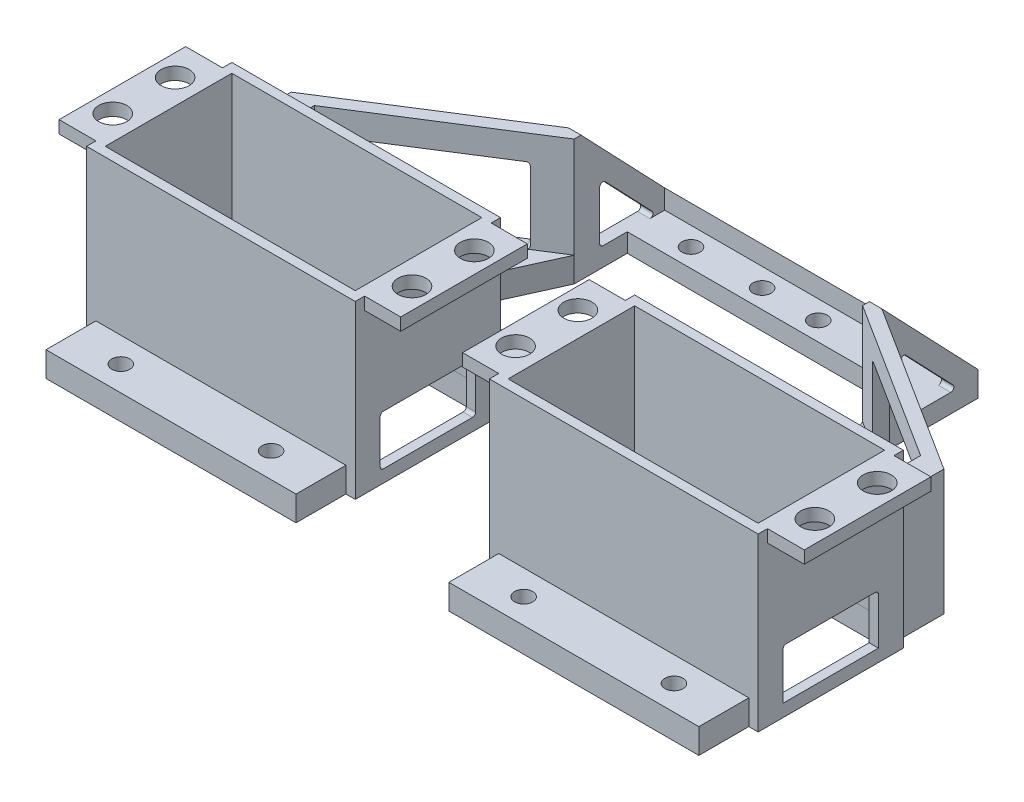
SolidWorks part; units mm, degrees
material "PLA"
ref_plane "Front Plane" through (0, 0, 0) normal (0, 0, 1) x (1, 0, 0)
ref_plane "Top Plane" through (0, 0, 0) normal (0, 1, 0) x (1, 0, 0)
ref_plane "Right Plane" through (0, 0, 0) normal (1, 0, 0) x (0, 0, -1)
sketch "Sketch1" plane through (0, 0, 0) normal (0, 1, 0) x (1, 0, 0)
  line L0 (-59.76, 0) -> (59.76, 0) construction
  line L1 (0, -37.87) -> (0, 37.87) construction
  line L2 (-52.3548, -24.6209) -> (-52.3524, -4.3209)
  line L5 (-52.3524, -4.3209) -> (-12.2524, -4.3257)
  line L8 (-59.76, -37.87) -> (-59.76, -14.47) construction
  line L9 (-59.76, -37.87) -> (59.76, -37.87) construction
  line L10 (-59.76, -37.87) -> (-59.76, 37.87) construction
  line L11 (-59.76, 37.87) -> (59.76, 37.87) construction
  line L12 (59.76, -37.87) -> (59.76, 37.87) construction
  line L13 (-12.2524, -4.3257) -> (-12.2548, -24.6257)
  line L14 (-12.2548, -24.6257) -> (-52.3548, -24.6209)
  line L15 (-53.8522, -2.8207) -> (-10.7522, -2.8259)
  line L16 (-10.7522, -2.8259) -> (-10.755, -26.1259)
  line L17 (-10.755, -26.1259) -> (-53.855, -26.1207)
  line L18 (-53.855, -26.1207) -> (-53.8522, -2.8207)
  line L19 (-52.3524, -2.8209) -> (-52.3524, 5.1743)
  line L20 (-52.3524, 5.1743) -> (-12.2524, 5.1743)
  line L21 (-12.2524, 5.1743) -> (-12.2524, -2.8257)
  line L22 (-52.3548, -26.1209) -> (-52.3548, -34.1257)
  line L23 (-52.3548, -34.1257) -> (-12.2548, -34.1257)
  line L24 (-12.2548, -34.1257) -> (-12.2548, -26.1257)
  line L25 (-25.1261, 37.87) -> (0, 37.87)
  line L26 (-25.1261, 37.87) -> (-25.1261, 22.4543)
  line L27 (-25.1261, 22.4543) -> (-52.3524, 5.1743)
  line L28 (0, 37.87) -> (0, 35.87)
  line L29 (0, 35.87) -> (-23.1261, 35.87)
  line L30 (-23.1261, 35.87) -> (-23.1261, 21.3549)
  line L31 (-23.1261, 21.3549) -> (-48.6201, 5.1743)
  point P5 (0, 0)
  point P6 (0, 0)
  point P7 (-59.76, -14.47)
  point P32 (0, 37.87)
  line B0 (-52.3548, -24.6209) -> (-52.3524, -4.3209) construction
  line B1 (-4.9588, -4.3265) -> (-59.7588, -4.32) construction
  line B2 (-4.9612, -24.6265) -> (-4.9588, -4.3265) construction
  line B3 (-12.2548, -24.6257) -> (-12.2524, -4.3257) construction
  line B4 (-4.9612, -24.6265) -> (-59.7612, -24.62) construction
  line B5 (-59.7588, -4.32) -> (-59.7612, -24.62) construction
  circle B6 centre (-8.3042, -19.4761) radius 2.25 construction
  circle B7 centre (-8.303, -9.4761) radius 2.25 construction
  circle B8 centre (-56.303, -9.4704) radius 2.25 construction
  circle B9 centre (-56.3042, -19.4704) radius 2.25 construction
  dimension "D1" = 119.52
  dimension "D2" = 75.74
  dimension "D3" = 1.5
  dimension "D4" = 23.4
  dimension "D5" = 8
  dimension "D6" = 8
  dimension "D7" = 2
  dimension "D8" = 2
  dimension "D9" = 2
  dimension "D10" = 17.28
sketch_block_instance "Block2-1"
sketch_block "Block2"
extrude "Boss-Extrude1" add sketch "Sketch1" along normal blind 4 contours L31 L30 L29 L28 L25 L26 L27 L20 | L21 L20 L19 L15 | L18 L17 L16 L15 L13 L14 L2 L5 | L23 L24 L17 L22 region at (-53.1023, 0, 3.3108) region at (-32.3004, 0, -1.1755) region at (-38.4085, 0, -13.2932) region at (-32.3068, 0, 30.1245)
sketch "Sketch2" plane through (0, 4, 0) normal (0, 1, 0) x (1, 0, 0)
  line L1 (-48.6201, 5.1743) -> (-23.1261, 21.3549)
  line L2 (-23.1261, 21.3549) -> (-23.1261, 35.87)
  line L3 (-23.1261, 35.87) -> (0, 35.87)
  line L4 (0, 35.87) -> (0, 37.87)
  line L5 (0, 37.87) -> (-25.1261, 37.87)
  line L6 (-25.1261, 37.87) -> (-25.1261, 22.4543)
  line L7 (-25.1261, 22.4543) -> (-52.3524, 5.1743)
  line L8 (-53.8522, -2.8207) -> (-10.7522, -2.8259)
  line L9 (-10.7522, -2.8259) -> (-10.755, -26.1259)
  line L10 (-10.755, -26.1259) -> (-53.855, -26.1207)
  line L11 (-53.855, -26.1207) -> (-53.8522, -2.8207)
  line L12 (-48.6201, 5.1743) -> (-48.6201, -2.8213)
  line L13 (-52.3548, -24.6209) -> (-12.2524, -24.6209)
  line L14 (-52.3548, -24.6209) -> (-52.3548, -4.3257)
  line L15 (-52.3548, -4.3257) -> (-12.2524, -4.3257)
  line L16 (-12.2524, -24.6209) -> (-12.2524, -4.3257)
  line L17 (-52.3524, 5.1743) -> (-52.3524, -2.8209)
  line M1 (-48.6201, 5.1743) -> (-23.1261, 21.3549)
  line M2 (-23.1261, 21.3549) -> (-23.1261, 35.87)
  line M3 (-23.1261, 35.87) -> (0, 35.87)
  line M4 (0, 35.87) -> (0, 37.87)
  line M5 (0, 37.87) -> (-25.1261, 37.87)
  line M6 (-25.1261, 37.87) -> (-25.1261, 22.4543)
  line M7 (-25.1261, 22.4543) -> (-52.3524, 5.1743)
  line M8 (-52.3524, 5.1743) -> (-52.3524, -2.8209)
extrude "Boss-Extrude3" add sketch "Sketch2" along normal blind 23.5 contours L12 L8 M1 M2 M3 M4 M5 M6 M7 M8 | L8 L9 L10 L11 | L14 L15 L16 L13 region at (-49.2832, 4, -1.1765)
sketch "Sketch4" plane through (0, 27.5, 0) normal (0, 1, 0) x (1, 0, 0)
  line L0 (-52.3548, -4.3257) -> (-59.7588, -4.32)
  line L1 (-59.7588, -4.32) -> (-59.7612, -24.62)
  line L2 (-59.7612, -24.62) -> (-52.3548, -24.6209)
  line L3 (-12.2524, -4.3257) -> (-4.9588, -4.3265)
  line L4 (-4.9588, -4.3265) -> (-4.9612, -24.6265)
  line L5 (-4.9612, -24.6265) -> (-12.2524, -24.6209)
  line L6 (-12.2524, -24.6209) -> (-12.2524, -4.3257)
  line L7 (-52.3548, -24.6209) -> (-52.3548, -4.3257)
  circle A0 centre (-56.303, -9.4704) radius 2.25
  circle A1 centre (-56.3042, -19.4704) radius 2.25
  circle A2 centre (-8.303, -9.4761) radius 2.25
  circle A3 centre (-8.3042, -19.4761) radius 2.25
extrude "Boss-Extrude4" add sketch "Sketch4" against normal blind 2
sketch "Sketch5" plane through (-10.7519, 0, -0.0013) normal (1, 0, 0.0001) x (0.0001, 0, -1)
  line L1 (-22.1271, 2) -> (-6.8271, 2)
  line L2 (-22.1271, 2) -> (-22.1271, 10)
  line L3 (-22.1271, 10) -> (-6.8271, 10)
  line L4 (-6.8271, 2) -> (-6.8271, 10)
  line L6 (-26.1271, 27.5) -> (-26.1271, 0) construction
  line L7 (-2.8271, 27.5) -> (-2.8271, 0) construction
  line L8 (-4.3271, 0) -> (-24.6271, 0) construction
  dimension "D1" = 4
  dimension "D2" = 4
  dimension "D3" = 2
  dimension "D4" = 8
extrude "Cut-Extrude1" cut sketch "Sketch5" against normal through all
sketch "Sketch6" plane through (0, 4, 0) normal (0, 1, 0) x (1, 0, 0)
  line L0 (-52.3548, -34.1257) -> (-12.2548, -34.1257) construction
  line L1 (-12.2548, -34.1257) -> (-12.2548, -26.1257) construction
  line L2 (-52.3548, -26.1209) -> (-52.3548, -34.1257) construction
  line L3 (-52.3524, -2.8209) -> (-52.3524, 5.1743) construction
  line L4 (-52.3524, 5.1743) -> (-12.2524, 5.1743) construction
  line L5 (-12.2524, 5.1743) -> (-12.2524, -2.8257) construction
  circle A0 centre (-44.3548, -30.1257) radius 1.45
  circle A1 centre (-20.2548, -30.1257) radius 1.45
  circle A2 centre (-44.3524, 1.1743) radius 1.45
  circle A3 centre (-20.2524, 1.1743) radius 1.45
  dimension "D1" = 2.9
  dimension "D2" = 2.9
  dimension "D4" = 8
  dimension "D5" = 8
  dimension "D6" = 4
  dimension "D7" = 2.9
  dimension "D8" = 8
  dimension "D9" = 4
  dimension "D10" = 2.9
  dimension "D11" = 8
  dimension "D12" = 4
  dimension "D3" = 4
extrude "Cut-Extrude2" cut sketch "Sketch6" against normal through all
sketch "Sketch7" plane through (-25.1261, 0, 0) normal (-1, 0, 0) x (0, 0, 1)
  line L3 (-22.4543, 27.5) -> (-22.4543, 0) construction
  line L5 (-22.4543, 20.1314) -> (2.8207, 20.1314)
  line L8 (-37.87, 27.5) -> (2.8207, 27.5)
  line L10 (2.8207, 27.5) -> (2.8207, 20.1314)
  line L18 (-37.87, 4) -> (-22.4543, 20.1314)
  line L20 (-37.87, 27.5) -> (-37.87, 4)
extrude "Cut-Extrude3" cut sketch "Sketch7" against normal through all and the other way through all
sketch "Sketch8" plane through (-25.1261, 0, 0) normal (-1, 0, 0) x (0, 0, 1)
  line L4 (-25.4543, 12.6499) -> (-34.676, 3)
  line L6 (-25.4543, 12.6499) -> (-34.676, 3)
  line L11 (-25.4543, 3) -> (-25.4543, 12.6499)
  line L12 (-25.4543, 3) -> (-25.4543, 12.6499)
  line L14 (-34.676, 3) -> (-25.4543, 3)
  line L18 (-34.676, 3) -> (-25.4543, 3)
  dimension "D1" = 3
extrude "Cut-Extrude4" cut sketch "Sketch8" against normal up to surface (2 mm away) up to face at (-23.1261, 9.2711, -27.3808)
sketch "Sketch9" plane through (0, 0, 0) normal (0, -1, 0) x (1, 0, 0)
  line L0 (0, -35.87) -> (0, -29.87)
  line L1 (0, -29.87) -> (-23.1261, -29.87)
  line L2 (-23.1261, -35.87) -> (-23.1261, -21.3549) construction
  line L3 (-23.1261, -29.87) -> (-23.1261, -35.87)
  line L4 (-23.1261, -35.87) -> (0, -35.87)
  dimension "D1" = 6
extrude "Boss-Extrude5" add sketch "Sketch9" against normal blind 4
sketch "Sketch10" plane through (0, 4, 0) normal (0, 1, 0) x (1, 0, 0)
  line L1 (-48.6201, 5.1743) -> (-12.2524, 5.1743) construction
  line L2 (-30.4362, 5.1743) -> (-48.6201, 5.1743)
  line L6 (-30.4362, 5.1743) -> (-23.1261, 21.3549)
  line L7 (-48.6201, 5.1743) -> (-23.1261, 21.3549)
extrude "Boss-Extrude6" add sketch "Sketch10" against normal blind 4
sketch "Sketch11" plane through (0, 3, 0) normal (0, 1, 0) x (1, 0, 0)
  line L0 (0, 29.87) -> (-23.1261, 29.87) construction
  line L1 (0, 35.87) -> (0, 29.87) construction
  circle A0 centre (-15.9049, 32.87) radius 1.45
  circle A1 centre (-4.5, 32.87) radius 1.45
  dimension "D1" = 2.9
  dimension "D2" = 3
  dimension "D3" = 2.9
  dimension "D4" = 3
  dimension "D5" = 4.5
extrude "Cut-Extrude5" cut sketch "Sketch11" against normal through all and the other way through all
mirror "Mirror1" about plane through (0, 0, 0) normal (1, 0, 0) of "Boss-Extrude6", "Boss-Extrude5", "Cut-Extrude4", "Cut-Extrude3", "Cut-Extrude2", "Cut-Extrude1", "Boss-Extrude4", "Boss-Extrude3", "Boss-Extrude1", "Cut-Extrude5"
sketch "Sketch12" plane through (-17.3741, 0, -27.3744) normal (-0.5359, 0, -0.8443) x (-0.8443, 0, 0.5359)
  line L4 (37.4286, 16.1314) -> (13.1816, 16.1314)
  line L6 (37.4286, 16.1314) -> (13.1816, 16.1314)
  line L8 (37.4286, 4) -> (37.4286, 16.1314)
  line L10 (13.1816, 16.1314) -> (13.1816, 4)
  line L11 (13.1816, 4) -> (37.4286, 4)
  line L12 (37.4286, 4) -> (37.4286, 16.1314)
  line L14 (13.1816, 16.1314) -> (13.1816, 4)
  line L15 (13.1816, 4) -> (37.4286, 4)
  dimension "D1" = 4
extrude "Cut-Extrude6" cut sketch "Sketch12" against normal up to surface (2 mm away) up to face at (-35.8731, 12.0657, -13.2646)
fillet "Fillet1" radius 0.5 4 edges at (-27.9675, 4, -19.4666) (-48.4393, 4, -6.4735) (-48.4393, 16.1314, -6.4735) (-27.9675, 16.1314, -19.4666)
fillet "Fillet2" radius 0.5 3 edges at (-24.1261, 3, -34.676) (-24.1261, 3, -25.4543) (-24.1261, 12.6499, -25.4543)
fillet "Fillet3" radius 0.5 8 edges at (-11.5027, 2, 6.8258) (-11.5045, 2, 22.1258) (-11.5034, 10, 22.1258) (-11.5025, 10, 6.8258) (-53.1027, 2, 6.8208) (-53.1045, 2, 22.1208) (-53.1046, 10, 22.1208) (-53.1037, 10, 6.8208)
sketch "Sketch13" plane through (17.3741, 0, -27.3744) normal (0.5359, 0, -0.8443) x (-0.8443, 0, -0.5359)
  line L8 (-13.1816, 4) -> (-13.1816, 16.1314)
  line L9 (-13.1816, 16.1314) -> (-37.4286, 16.1314)
  line L10 (-37.4286, 16.1314) -> (-37.4286, 4)
  line L11 (-37.4286, 4) -> (-13.1816, 4)
  line L12 (-13.1816, 4) -> (-13.1816, 16.1314)
  line L14 (-37.4286, 16.1314) -> (-37.4286, 4)
  line L15 (-37.4286, 4) -> (-13.1816, 4)
  line L16 (-13.1816, 16.1314) -> (-37.4286, 16.1314)
  dimension "D1" = 4
extrude "Cut-Extrude7" cut sketch "Sketch13" against normal up to surface (2 mm away) up to face at (35.8731, 12.0657, -13.2646)
fillet "Fillet4" radius 0.5 15 edges at (12.2534, 4, 22.1257) (12.2525, 4, 6.8257) (11.5025, 10, 6.8258) (11.5034, 10, 22.1258) (52.3537, 4, 6.8209) (53.1037, 10, 6.8208) (53.1046, 10, 22.1208) (52.3546, 4, 22.1209) (48.4393, 4, -6.4735) (48.4393, 16.1314, -6.4735) (27.9675, 16.1314, -19.4666) (27.9675, 4, -19.4666) (24.1261, 3, -25.4543) (24.1261, 12.6499, -25.4543) (24.1261, 3, -34.676)
sketch "Sketch14" plane through (0, 4, 0) normal (0, 1, 0) x (1, 0, 0)
  line L6 (23.1261, 35.87) -> (-23.1261, 35.87)
  line L7 (-23.1261, 35.87) -> (-23.1261, 33.7204)
  line L8 (-23.1261, 33.7204) -> (-23.1261, 29.87)
  line L9 (-23.1261, 29.87) -> (23.1261, 29.87)
  line L10 (23.1261, 29.87) -> (23.1261, 33.7204)
  line L11 (23.1261, 33.7204) -> (23.1261, 35.87)
  line L12 (23.1261, 35.87) -> (-23.1261, 35.87)
  line L13 (-23.1261, 35.87) -> (-23.1261, 33.7204)
  line L14 (-23.1261, 33.7204) -> (-23.1261, 29.87)
  line L15 (-23.1261, 29.87) -> (23.1261, 29.87)
  line L16 (23.1261, 29.87) -> (23.1261, 33.7204)
  line L17 (23.1261, 33.7204) -> (23.1261, 35.87)
  dimension "D1" = 0
extrude "Cut-Extrude8" cut sketch "Sketch14" against normal up to surface (1 mm away) up to face at (23.9261, 3, -29.7584)
